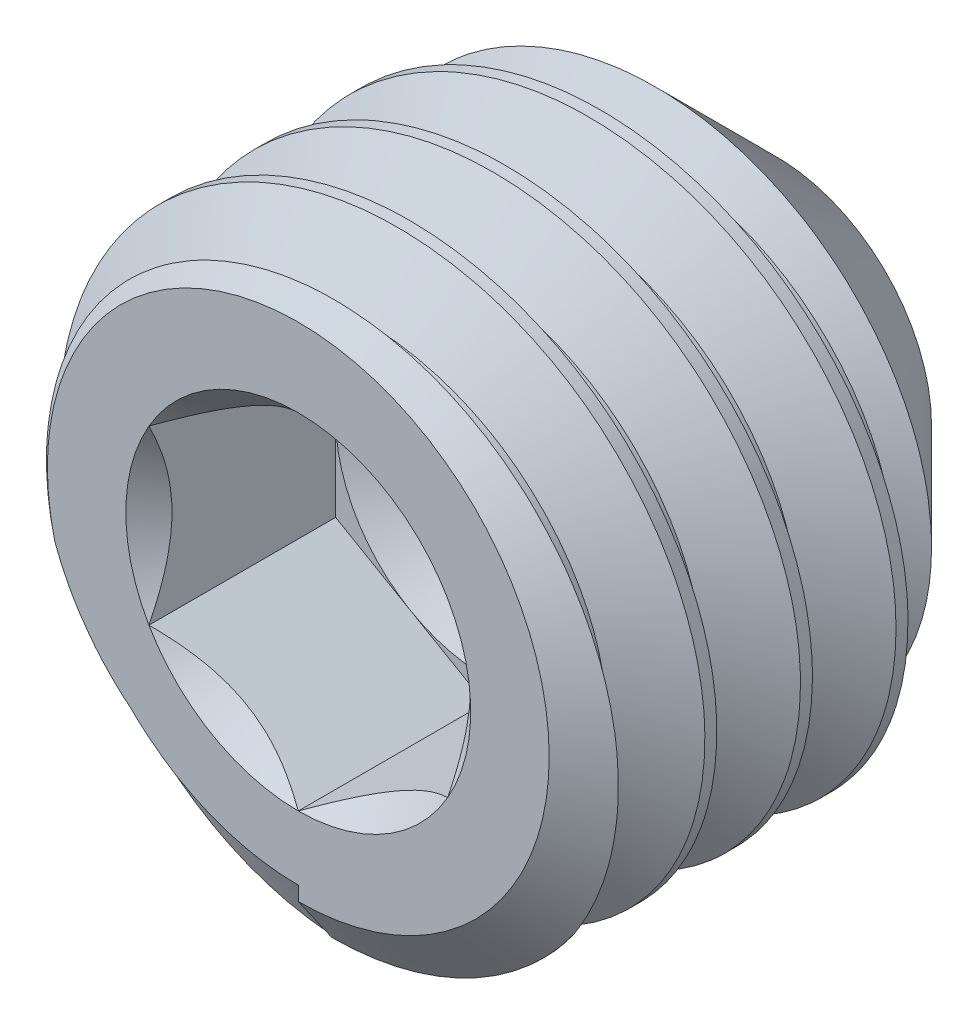
SolidWorks part; units mm, degrees
other "Imported1" parameters "D3"=4.4, "D1"=46.842, "Length"=4, "Drive Size"=2.5, "Thread Size"=5, "Thread Pitch"=0.8, "D2"=0.0866, "hex Depth"=1.5625, "Dia"=12, "D4"=2.3829, "Cup Point Dia"=3.3528, "D5"=1.436, "D6"=1.4986, "D7"=5.0014, "Pitch"=1.75
material "Plain Carbon Steel"
ref_plane "Front" through (0, 0, 0) normal (0, 0, 1) x (1, 0, 0)
ref_plane "Top" through (0, 0, 0) normal (0, 1, 0) x (1, 0, 0)
ref_plane "Right" through (0, 0, 0) normal (1, 0, 0) x (0, 0, -1)
sketch "Sketch1" plane through (0, 0, 0) normal (1, 0, 0) x (0, 0, -1)
  line L0 (2, 2.5) -> (-2, 2.5) construction
  line L1 (-2, 2.5) -> (-2, -2.5) construction
  line L2 (-2, -2.5) -> (2, -2.5) construction
  line L3 (2, -2.5) -> (2, 2.5) construction
  line L4 (-2, 1.25) -> (-2, -1.25) construction
  line L5 (1.95, 2.5866) -> (2.75, 2.5866) construction
  line L6 (1.95, 2.5866) -> (2, 2.5) construction
  line L7 (2, 2.5) -> (2.7, 2.5) construction
  line L8 (2.7, 2.5) -> (2.75, 2.5866) construction
  line L9 (2, 2.5) -> (2.35, 1.8938) construction
  line L10 (2.35, 1.8938) -> (2.7, 2.5) construction
  line L11 (2.3, 1.9804) -> (2.4, 1.9804) construction
  line L12 (2.35, 2.5866) -> (2.35, 2.5) construction
  line L13 (2.35, 1.9804) -> (2.35, 1.8938) construction
  point P3 (0, 2.5)
  point P24 (-2, 0)
  point P25 (-2, 0)
  dimension "D1" = 0.1
sketch "Sketch11" plane through (0, 0, 0) normal (1, 0, 0) x (0, 0, -1)
  line L0 (-2, 0) -> (-2, 2.1)
  line L1 (-2, 2.1) -> (-1.7199, 2.5)
  line L2 (-1.7199, 2.5) -> (0.8, 2.5)
  line L3 (0.8, 2.5) -> (2, 1.3)
  line L4 (2, 1.3) -> (1.2189, 0)
  line L5 (1.2189, 0) -> (-2, 0)
  line L6 (1.2189, 0) -> (2, 0) construction
  line L7 (2, 0) -> (2, 1.3) construction
  line L8 (2, -1.3) -> (1.2189, 0) construction
  line L9 (-1.7199, -2.5) -> (0.8, -2.5) construction
  line L10 (-2, -2.5) -> (2, -2.5) construction
  line L11 (-2, 2.5) -> (-2, -2.5) construction
  line L12 (2, -2.5) -> (2, 2.5) construction
  point P11 (-0.8, -2.5)
  point P12 (-2, 2.5)
  dimension "D3" = 35
  dimension "D5" = 118
  dimension "D6" = 45
  dimension "D1" = 0.4
  dimension "D2" = 2.8
  dimension "D4" = 1.2
revolve "Revolve1" add sketch "Sketch11" angle 360 about L6
sketch "Sketch2" plane through (0, 0, 2) normal (0, 0, 1) x (1, 0, 0)
  line L1 (0, 1.4434) -> (-1.25, 0.7217)
  line L2 (-1.25, 0.7217) -> (-1.25, -0.7217)
  line L3 (-1.25, -0.7217) -> (0, -1.4434)
  line L4 (0, -1.4434) -> (1.25, -0.7217)
  line L5 (1.25, -0.7217) -> (1.25, 0.7217)
  line L6 (1.25, 0.7217) -> (0, 1.4434)
  circle A0 centre (0, 0) radius 1.25 construction
  circle A1 centre (0, 0) radius 2.5 construction
extrude "Cut-Extrude1" cut sketch "Sketch2" against normal blind 1.5625
sketch "Sketch3" plane through (0, 0, 2) normal (0, 0, 1) x (1, 0, 0)
  circle A0 centre (0, 0) radius 1.4434
extrude "Cut-Extrude2" cut sketch "Sketch3" against normal through all draft 45
sketch "Sketch4" plane through (0, 0, 0.4375) normal (0, 0, 1) x (1, 0, 0)
  circle A0 centre (0, 0) radius 1.25 construction
  circle A1 centre (0, 0) radius 1.25
extrude "Cut-Extrude3" cut sketch "Sketch4" against normal through all draft 60
sketch "Sketch13" plane through (0, 0, 0) normal (1, 0, 0) x (0, 0, -1)
  line L0 (0, -2.5) -> (0, 2.5) construction
  line L2 (-1.7199, 2.5) -> (0.8, 2.5) construction
  line L4 (1.2189, 0) -> (-2, 0) construction
  point P0 (-3.7811, 0)
  point P4 (0, 0)
  point P9 (3.7811, 0)
  dimension "D1" = 5
ref_plane "Plane1" through (0, 0, -2) normal (0, 0, 1) x (1, 0, 0)
sketch "Sketch5" plane through (0, 0, -2) normal (0, 0, 1) x (1, 0, 0)
  circle A0 centre (0, 0) radius 2.5 construction
  circle A1 centre (0, 0) radius 2.5
curve "Helix/Spiral1" pitch 0.8 height 4.4 radius 2.5 centre (0, 0, -2) axis (0, 0, 1) start towards (0, 1, 0)
sketch "Sketch6" plane through (0, 0, 0) normal (1, 0, 0) x (0, 0, -1)
  line L0 (1.975, 2.5433) -> (2.725, 2.5433)
  line L1 (1.95, 2.5866) -> (2, 2.5) construction
  line L2 (2.7, 2.5) -> (2.75, 2.5866) construction
  line L3 (2.725, 2.5433) -> (2.4, 1.9804)
  line L4 (2.4, 1.9804) -> (2.3, 1.9804)
  line L5 (2.3, 1.9804) -> (1.975, 2.5433)
sweep "Cut-Sweep1" cut profiles "Sketch6" path "Helix/Spiral1"
equation "\"D3@Helix/Spiral1\" = \"Length@Sketch1\" * 1.1"
equation "\"hex Depth@Cut-Extrude1\"=\"Drive Size@Sketch1\" * .625"
equation "\"D1@Sketch11\" = \"Thread Pitch@Sketch1\" * .5"
equation "\"D2@Sketch11\" = \"Thread Pitch@Sketch1\" * 3.5"
equation "\"D1@Helix/Spiral1\" = \"Thread Pitch@Sketch1\""
equation "\"D4@Sketch11\" = \"Thread Pitch@Sketch1\" * 1.5"
equation "\"D1@Sketch1\" = \"Thread Pitch@Sketch1\" / 8"
equation "\"D1@Sketch13\"=\"Thread Size@Sketch1\""
